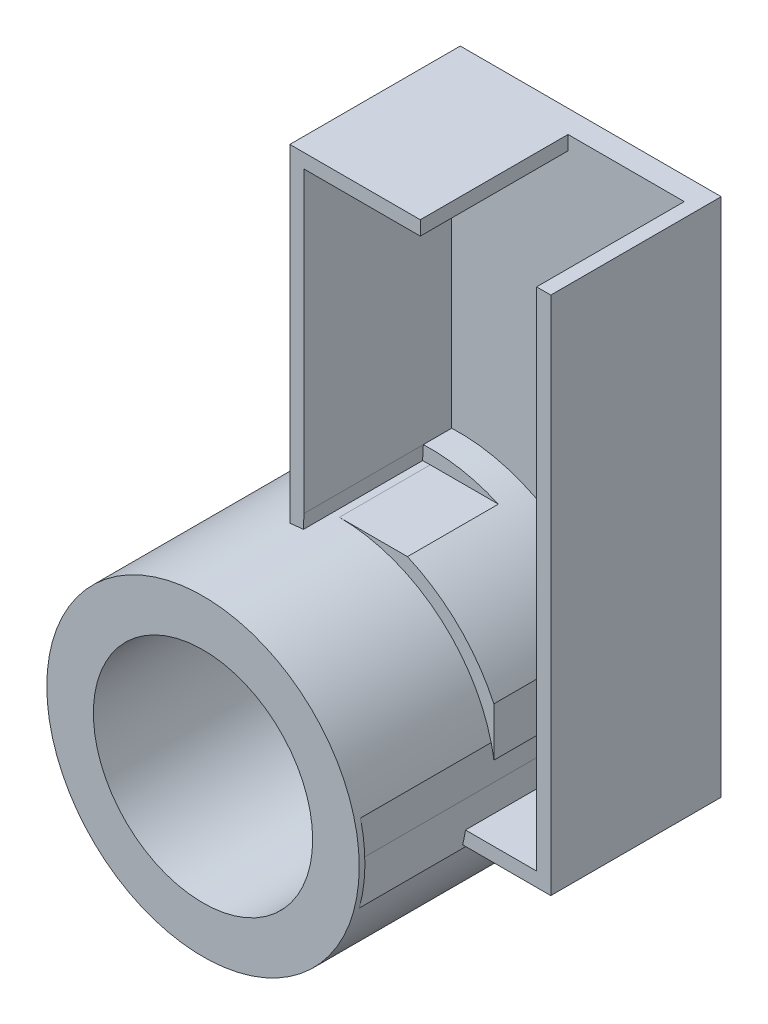
SolidWorks part; units mm, degrees
note: The reader was unsure of these and kept them because the rebuilt part matched: shared geometry of "Sketch2<4>", "Sketch2<5>", "Sketch2<6>".
ref_plane "Front Plane" through (0, 0, 0) normal (0, 0, 1) x (1, 0, 0)
ref_plane "Top Plane" through (0, 0, 0) normal (0, 1, 0) x (1, 0, 0)
ref_plane "Right Plane" through (0, 0, 0) normal (1, 0, 0) x (0, 0, -1)
sketch "Sketch2" plane through (0, 0, 0) normal (0, 0, 1) x (1, 0, 0)
  line L0 (0, 0) -> (0, 10) construction
  line L1 (-10.4, 20.4) -> (10.4, 20.4) construction
  line L2 (-10.4, 20.4) -> (-10.4, -20.4) construction
  line L3 (-10.4, -20.4) -> (6.1262, -20.4) construction
  line L4 (10.4, 20.4) -> (10.4, -20.4) construction
  line L5 (-10.4, 20.4) -> (10.4, -20.4) construction
  line L6 (-10.4, -20.4) -> (10.4, 20.4) construction
  line L7 (0, 0) -> (0, -55) construction
  line L8 (10.4, 20.4) -> (-10.4, 20.4)
  line L9 (-10.4, 20.4) -> (-10.4, -20.4)
  line L10 (-10.4, -20.4) -> (10.4, -20.4)
  line L11 (10.4, -20.4) -> (10.4, 20.4)
  circle A0 centre (0, -55) radius 50 construction
  circle A1 centre (0, -55) radius 16.25
  circle A2 centre (0, -55) radius 19.5
  arc A3 (-24.6949, -42.9) -> (24.6949, -42.9) centre (0, -55) ccw
  arc A4 (24.6949, -12.1) -> (-24.6949, -12.1) centre (0, 0) ccw
  arc A5 (-24.6949, -42.9) -> (-24.6949, -12.1) centre (-56.1249, -27.5) ccw
  arc A6 (24.6949, -12.1) -> (24.6949, -42.9) centre (56.1249, -27.5) ccw
  point P3 (0, 0)
  dimension "D1" = 40.8
  dimension "D3" = 32.5
  dimension "D4" = 39
  dimension "D6" = 55
  dimension "D7" = 55
  dimension "D9" = 70
  dimension "D10" = 70
  dimension "D11" = 100
  dimension "D2" = 20.8
  dimension "D5" = 10
  dimension "D8" = 55
extrude "Boss-Extrude1" add sketch "Sketch2" along normal mid plane 48 contours A4 A5 A3 A6
extrude "Cut-Extrude1" cut sketch "Sketch2<4>" against normal through all and the other way through all contours A1
sketch "Sketch2<4>" plane through (0, 0, 0) normal (0, 0, 1) x (1, 0, 0) same geometry as "Sketch2"
extrude "Cut-Extrude2" cut sketch "Sketch2<5>" against normal blind 48 and the other way blind 3 contours A2 A1
sketch "Sketch2<5>" plane through (0, 0, 0) normal (0, 0, 1) x (1, 0, 0) same geometry as "Sketch2"
extrude "Cut-Extrude3" cut sketch "Sketch2<6>" along normal blind 48 and the other way blind 16 contours L8 L9 L10 L11
sketch "Sketch2<6>" plane through (0, 0, 0) normal (0, 0, 1) x (1, 0, 0) same geometry as "Sketch2"
sketch "Sketch3" plane through (0, 0, 24) normal (0, 0, 1) x (1, 0, 0)
  line L0 (0, 0) -> (0, 27.5) construction
  line L1 (10.4, 20.4) -> (-10.4, 20.4) construction
  line L2 (-4.25, 34.6) -> (4.25, 34.6)
  line L3 (-4.25, 34.6) -> (-4.25, 20.4)
  line L4 (-4.25, 20.4) -> (4.25, 20.4)
  line L5 (4.25, 34.6) -> (4.25, 20.4)
  line L6 (-4.25, 34.6) -> (4.25, 20.4) construction
  line L7 (-4.25, 20.4) -> (4.25, 34.6) construction
  arc A0 (24.6949, -12.1) -> (-24.6949, -12.1) centre (0, 0) ccw construction
  dimension "D1" = 8.5
extrude "Cut-Extrude4" cut sketch "Sketch3" against normal blind 40
ref_plane "Plane1" through (24.6949, -42.9, -24) normal (-0.44, 0.898, 0) x (0.898, 0.44, 0)
sketch "Sketch7" plane through (0, 0, -24) normal (0, 0, -1) x (-1, 0, 0)
  circle A0 centre (0, -55) radius 27.5
  circle A1 centre (0, -55) radius 18.9
extrude "Boss-Extrude2" add sketch "Sketch7" along normal blind 1
sketch "Sketch8" plane through (0, 0, 24) normal (0, 0, 1) x (1, 0, 0)
  line L1 (-115.7459, 51.1118) -> (65.6143, 51.1118)
  line L2 (-115.7459, 51.1118) -> (-115.7459, -104.1004)
  line L3 (-115.7459, -104.1004) -> (65.6143, -104.1004)
  line L4 (65.6143, 51.1118) -> (65.6143, -104.1004)
extrude "Cut-Extrude5" cut sketch "Sketch8" against normal blind 48
sketch "Sketch9" plane through (0, 0, -24) normal (0, 0, 1) x (1, 0, 0)
  circle A0 centre (0, -55) radius 18.9
  circle A1 centre (0, -55) radius 27.5
extrude "Boss-Extrude3" add sketch "Sketch9" along normal blind 48
sketch "Sketch10" plane through (0, 0, 24) normal (0, 0, 1) x (1, 0, 0)
  line L3 (26.5103, -55) -> (26.7179, -48.4883)
  line L4 (26.5103, -55) -> (26.5103, -62.3113)
  line L6 (0, -81.9229) -> (5.6041, -81.9229)
  line L7 (5.6041, -81.9229) -> (-5.6041, -81.9229)
  circle A0 centre (0, -55) radius 27.5 construction
  arc A1 (-5.6041, -81.9229) -> (-27.5, -55) centre (0, -55) ccw
  circle M1 centre (0, -55) radius 27.5
extrude "Cut-Extrude6" cut sketch "Sketch10" against normal blind 48 contours L3 L4 M1 | L6 L7 M1
sketch "Sketch11" plane through (0, 0, 24) normal (0, 0, 1) x (1, 0, 0)
  line L0 (74.0848, -18.7) -> (-24.6949, -67.1) construction
  line L1 (26.5103, -61.5678) -> (42.2172, -61.5678)
  line L2 (25.0123, -61.5678) -> (42.2172, -61.5678) construction
  line L3 (26.5103, -55) -> (26.5103, -62.3113) construction
  line L4 (42.2172, -61.5678) -> (42.2172, 29.9887)
  line L5 (42.2172, 29.9887) -> (-3.7193, 29.9887)
  line L6 (-3.7193, 29.9887) -> (-3.7193, -27.7527)
  line L7 (-3.7193, 29.9887) -> (-3.7193, -29.8028) construction
  circle A0 centre (0, -55) radius 18.9
  circle A1 centre (0, -55) radius 27.5
  arc M2 (26.7179, -48.4883) -> (-5.6041, -81.9229) centre (0, -55) ccw
extrude "Boss-Extrude4" add sketch "Sketch11" against normal blind 4 contours A1 L1 L4 L5 L6 M2
sketch "Sketch16" plane through (0, 0, 24) normal (0, 0, -1) x (-1, 0, 0)
  line L0 (-26.7042, -61.5678) -> (-42.2172, -61.5678)
  line L1 (-42.2172, 29.9887) -> (-42.2172, -61.5678)
  line L2 (-42.2172, 29.9887) -> (3.7193, 29.9887)
  line L3 (3.7193, 29.9887) -> (3.7193, -27.7527)
  arc A0 (3.7193, -27.7527) -> (-26.7042, -61.5678) centre (0, -55) ccw
extrude "Extrude-Thin2" add sketch "Sketch16" along normal blind 30 thin
sketch "Sketch17" plane through (0, 0, -6) normal (0, 0, -1) x (-1, 0, 0)
  line L0 (1.3487, -27.5331) -> (1.2193, -25.0248)
  line L1 (-29.7229, -59.0678) -> (-27.1975, -59.0678)
  arc A0 (1.2193, -25.0248) -> (-29.7229, -59.0678) centre (0, -55) ccw
  arc A1 (1.2193, -25.0248) -> (-29.7229, -59.0678) centre (0, -55) ccw construction
  arc A2 (-27.1975, -59.0678) -> (1.3487, -27.5331) centre (0, -55) cw
  arc A3 (-26.7179, -48.4883) -> (-26.7042, -61.5678) centre (0, -55) ccw construction
extrude "Cut-Extrude8" cut sketch "Sketch17" against normal blind 21
sketch "Sketch18" plane through (0, 0, 20) normal (0, 0, -1) x (-1, 0, 0)
  line L0 (0, -27.5) -> (-27.1975, -27.5)
  line L2 (-27.1975, -59.0678) -> (-27.1975, -27.5)
  line L3 (24.6949, -67.1) -> (-74.0848, -18.7) construction
  arc A0 (1.3487, -27.5331) -> (-26.7179, -48.4883) centre (0, -55) ccw construction
  circle A1 centre (0, -55) radius 27.5 construction
  arc A2 (0, -27.5) -> (-27.1975, -59.0678) centre (0, -55) ccw
extrude "Boss-Extrude5" add sketch "Sketch18" along normal blind 21
sketch "Sketch19" plane through (0, 0, -6) normal (0, 0, -1) x (-1, 0, 0)
  line L0 (-39.7172, 27.4887) -> (-39.7172, 29.9887)
  line L1 (3.7193, 29.9887) -> (-42.2172, 29.9887) construction
  line L2 (-39.7172, 29.9887) -> (-19.249, 29.9887)
  line L3 (-19.249, 29.9887) -> (-19.249, 27.4887)
  line L4 (1.2193, 27.4887) -> (-39.7172, 27.4887) construction
  line L5 (-19.249, 27.4887) -> (-39.7172, 27.4887)
extrude "Cut-Extrude9" cut sketch "Sketch19" against normal blind 21
sketch "Sketch20" plane through (0, 0, 15) normal (0, 0, -1) x (-1, 0, 0)
  line L0 (-19.249, 29.9887) -> (-39.7172, 29.9887)
  line L1 (-39.7172, 29.9887) -> (-39.7172, 27.4887)
  line L2 (-39.7172, 27.4887) -> (-19.249, 27.4887) construction
  line L3 (-39.7172, 27.4887) -> (-19.249, 27.4887)
  line L4 (-19.249, 27.4887) -> (-19.249, 29.9887)
extrude "Cut-Extrude10" cut sketch "Sketch20" against normal blind 5
sketch "Sketch21" plane through (0, 0, 24) normal (0, 0, 1) x (1, 0, 0)
  circle A0 centre (0, -55) radius 27.5
  circle A1 centre (0, -55) radius 7.25
extrude "Boss-Extrude6" add sketch "Sketch21" against normal blind 3
ref_plane "Plane2" through (0, 0, 34) normal (0, 0, 1) x (1, 0, 0)
mirror "Mirror1" about plane through (0, 0, 34) normal (0, 0, 1) of bodies 117
sketch "Sketch24" plane through (0, 0, 24) normal (0, 0, 1) x (1, 0, 0)
  line L0 (42.2172, 29.9887) -> (-3.7193, 29.9887) construction
  line L1 (42.2172, 29.9887) -> (-312.7615, 29.9887)
  line L2 (42.2172, 29.9887) -> (42.2172, -106.8971)
  line L3 (42.2172, -106.8971) -> (-312.7615, -106.8971)
  line L4 (-312.7615, 29.9887) -> (-312.7615, -106.8971)
extrude "Cut-Extrude13" cut sketch "Sketch24" against normal blind 110
sketch "Sketch25" plane through (0, 0, 93) normal (0, 0, 1) x (1, 0, 0)
  circle A0 centre (0, -55) radius 19.3
extrude "Cut-Extrude14" cut sketch "Sketch25" against normal blind 46
